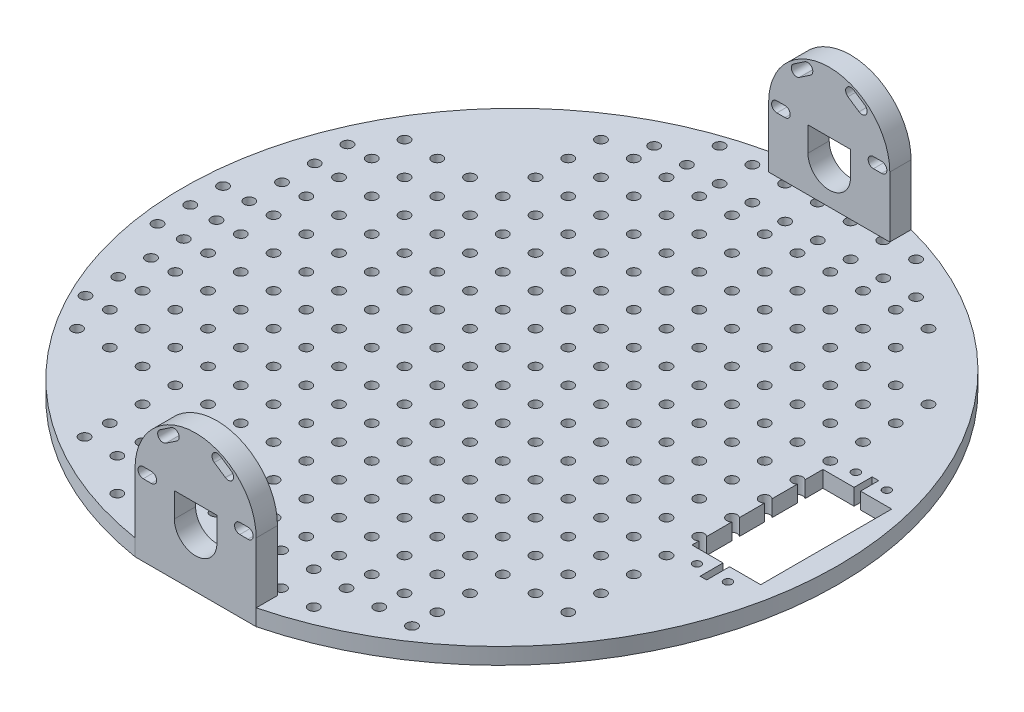
SolidWorks part; units mm, degrees
ref_plane "Ön Düzlem" through (0, 0, 0) normal (0, 0, 1) x (1, 0, 0)
ref_plane "Üst Düzlem" through (0, 0, 0) normal (0, 1, 0) x (1, 0, 0)
ref_plane "Sağ Düzlem" through (0, 0, 0) normal (1, 0, 0) x (0, 0, -1)
sketch "Çizim1" plane through (0, 0, 0) normal (0, 0, 1) x (1, 0, 0)
  circle A0 centre (0, 0) radius 18.5
  dimension "D1" = 37
extrude "Yükseklik-Ekstrüzyon1" add sketch "Çizim1" along normal blind 6.5
sketch "Çizim2" plane through (0, 0, 6.5) normal (0, 0, 1) x (1, 0, 0)
  line L0 (0, 0) -> (0, -7.5) construction
  line L1 (6.5, 0) -> (6.5, -7.5)
  line L2 (-6.5, 0) -> (-6.5, -7.5)
  line L3 (-6.5, 0) -> (6.5, 0)
  line L4 (-16, 0) -> (-13.5, 0) construction
  line L5 (-16, 1.6) -> (-13.5, 1.6)
  line L6 (-16, -1.6) -> (-13.5, -1.6)
  line L7 (16, 0) -> (13.5, 0) construction
  line L8 (16, -1.6) -> (13.5, -1.6)
  line L9 (16, 1.6) -> (13.5, 1.6)
  line L10 (6.6131, 14.8617) -> (9.9935, 12.5729) construction
  line L11 (7.5102, 16.1866) -> (10.8905, 13.8978)
  line L12 (5.7161, 13.5368) -> (9.0964, 11.2481)
  line L13 (-6.6131, 14.8617) -> (-9.9935, 12.5729) construction
  line L14 (-7.5102, 16.1866) -> (-10.8905, 13.8978)
  line L15 (-5.7161, 13.5368) -> (-9.0964, 11.2481)
  arc A0 (-16, 1.6) -> (-16, -1.6) centre (-16, 0) ccw
  arc A1 (-6.5, -7.5) -> (6.5, -7.5) centre (0, -7.5) ccw
  circle A2 centre (0, 0) radius 18.5 construction
  arc A3 (-13.5, -1.6) -> (-13.5, 1.6) centre (-13.5, 0) ccw
  arc A4 (16, -1.6) -> (16, 1.6) centre (16, 0) ccw
  arc A5 (13.5, 1.6) -> (13.5, -1.6) centre (13.5, 0) ccw
  arc A6 (7.5102, 16.1866) -> (5.7161, 13.5368) centre (6.6131, 14.8617) ccw
  arc A7 (9.0964, 11.2481) -> (10.8905, 13.8978) centre (9.9935, 12.5729) ccw
  arc A8 (-7.5102, 16.1866) -> (-5.7161, 13.5368) centre (-6.6131, 14.8617) cw
  arc A9 (-9.0964, 11.2481) -> (-10.8905, 13.8978) centre (-9.9935, 12.5729) cw
  point P3 (0, 0)
  point P6 (-14.75, 0)
  point P17 (14.75, 0)
  point P24 (8.3033, 13.7173)
  point P43 (-8.3033, 13.7173)
  dimension "D1" = 6.5
  dimension "D2" = 7.5
  dimension "D3" = 1.6
  dimension "D4" = 1.6
  dimension "D9" = 1.6
  dimension "D5" = 2.5
  dimension "D6" = 2.5
  dimension "D7" = 13.5
  dimension "D8" = 13.5
extrude "Kes-Ekstrüzyon1" cut sketch "Çizim2" against normal blind 6.5
sketch "Çizim3" plane through (0, 0, 0) normal (0, 0, -1) x (-1, 0, 0)
  line L0 (18.5, 0) -> (18.5, -18.5)
  line L1 (18.5, -18.5) -> (-18.5, -18.5)
  line L2 (-18.5, -18.5) -> (-18.5, 0)
  circle A0 centre (0, 0) radius 18.5 construction
  circle A2 centre (0, 0) radius 18.5
  circle A3 centre (0, 0) radius 18.5
  circle M22 centre (0, 0) radius 18.5
  dimension "D1" = 0
extrude "Yükseklik-Ekstrüzyon2" add sketch "Çizim3" against normal blind 6.5 contours L2 L1 M22 | L1 L0 M22 region at (-14.3677, -14.3677, 0) region at (14.3677, -14.3677, 0)
sketch "Çizim4" plane through (0, 0, 6.5) normal (0, 0, 1) x (1, 0, 0)
  line L1 (-18.5, -18.5) -> (18.5, -18.5)
  line L2 (-18.5, -18.5) -> (-18.5, -22.5)
  line L3 (-18.5, -22.5) -> (18.5, -22.5)
  line L4 (18.5, -18.5) -> (18.5, -22.5)
  dimension "D1" = 4
extrude "Yükseklik-Ekstrüzyon3" add sketch "Çizim4" along normal blind 30 and the other way up to surface (6.5 mm away) other way up to face at (-14.75, 0, 0)
sketch "Çizim5" plane through (0, -22.5, 0) normal (0, -1, 0) x (1, 0, 0)
  line L1 (-18.5, 0) -> (18.4954, 0)
  line L2 (-18.5, 0) -> (-18.5, 200)
  line L3 (-18.5, 200) -> (18.4954, 200)
  line L4 (18.4954, 0) -> (18.4954, 200)
  dimension "D1" = 200
extrude "Yükseklik-Ekstrüzyon4" add sketch "Çizim5" against normal up to surface (4 mm away) up to face at (0, -18.5, 21.5)
sketch "Çizim10" plane through (0, 0, 200) normal (0, 0, 1) x (1, 0, 0)
  line L0 (5.7161, 13.5368) -> (9.0964, 11.2481) construction
  line L1 (10.8905, 13.8978) -> (7.5102, 16.1866) construction
  line L2 (-7.5102, 16.1866) -> (-10.8905, 13.8978) construction
  line L3 (-18.5, 0) -> (-18.5, -18.5)
  line L4 (-18.5, -18.5) -> (18.5, -18.5)
  line L5 (18.5, -18.5) -> (18.5, 0)
  line L6 (-18.5, 0) -> (-18.5, -18.5)
  line L7 (-18.5, -18.5) -> (18.5, -18.5)
  line L8 (18.5, -18.5) -> (18.5, 0)
  line L9 (-9.0964, 11.2481) -> (-5.7161, 13.5368) construction
  line L10 (-13.5, 1.6) -> (-16, 1.6) construction
  line L11 (-16, -1.6) -> (-13.5, -1.6) construction
  line L12 (6.5, -7.5) -> (6.5, 0) construction
  line L13 (13.5, -1.6) -> (16, -1.6) construction
  line L14 (16, 1.6) -> (13.5, 1.6) construction
  line L15 (6.5, 0) -> (-6.5, 0) construction
  line L16 (-6.5, 0) -> (-6.5, -7.5) construction
  line L17 (5.7161, 13.5368) -> (9.0964, 11.2481)
  line L18 (10.8905, 13.8978) -> (7.5102, 16.1866)
  line L19 (-7.5102, 16.1866) -> (-10.8905, 13.8978)
  line L20 (-9.0964, 11.2481) -> (-5.7161, 13.5368)
  line L21 (-13.5, 1.6) -> (-16, 1.6)
  line L22 (-16, -1.6) -> (-13.5, -1.6)
  line L23 (6.5, -7.5) -> (6.5, 0)
  line L24 (13.5, -1.6) -> (16, -1.6)
  line L25 (16, 1.6) -> (13.5, 1.6)
  line L26 (6.5, 0) -> (-6.5, 0)
  line L27 (-6.5, 0) -> (-6.5, -7.5)
  arc A0 (9.0964, 11.2481) -> (10.8905, 13.8978) centre (9.9935, 12.5729) ccw construction
  arc A1 (18.5, 0) -> (-18.5, 0) centre (0, 0) ccw
  arc A2 (18.5, 0) -> (-18.5, 0) centre (0, 0) ccw
  arc A3 (7.5102, 16.1866) -> (5.7161, 13.5368) centre (6.6131, 14.8617) ccw construction
  arc A4 (-5.7161, 13.5368) -> (-7.5102, 16.1866) centre (-6.6131, 14.8617) ccw construction
  arc A5 (-10.8905, 13.8978) -> (-9.0964, 11.2481) centre (-9.9935, 12.5729) ccw construction
  arc A6 (-13.5, -1.6) -> (-13.5, 1.6) centre (-13.5, 0) ccw construction
  arc A7 (-16, 1.6) -> (-16, -1.6) centre (-16, 0) ccw construction
  arc A8 (-6.5, -7.5) -> (6.5, -7.5) centre (0, -7.5) ccw construction
  arc A9 (16, -1.6) -> (16, 1.6) centre (16, 0) ccw construction
  arc A10 (13.5, 1.6) -> (13.5, -1.6) centre (13.5, 0) ccw construction
  arc A11 (9.0964, 11.2481) -> (10.8905, 13.8978) centre (9.9935, 12.5729) ccw
  arc A12 (7.5102, 16.1866) -> (5.7161, 13.5368) centre (6.6131, 14.8617) ccw
  arc A13 (-5.7161, 13.5368) -> (-7.5102, 16.1866) centre (-6.6131, 14.8617) ccw
  arc A14 (-10.8905, 13.8978) -> (-9.0964, 11.2481) centre (-9.9935, 12.5729) ccw
  arc A15 (-13.5, -1.6) -> (-13.5, 1.6) centre (-13.5, 0) ccw
  arc A16 (-16, 1.6) -> (-16, -1.6) centre (-16, 0) ccw
  arc A17 (-6.5, -7.5) -> (6.5, -7.5) centre (0, -7.5) ccw
  arc A18 (16, -1.6) -> (16, 1.6) centre (16, 0) ccw
  arc A19 (13.5, 1.6) -> (13.5, -1.6) centre (13.5, 0) ccw
  dimension "D1" = 0
extrude "Yükseklik-Ekstrüzyon6" add sketch "Çizim10" against normal blind 6.5
sketch "Çizim12" plane through (0, -18.5, 0) normal (0, 1, 0) x (1, 0, 0)
  line L0 (-18.5, 0) -> (-18.5, -200)
  arc A0 (-18.5, 0) -> (-18.5, -200) centre (-2.5422, -100) ccw
extrude "Yükseklik-Ekstrüzyon7" add sketch "Çizim12" against normal up to surface (4 mm away) up to face at (6.1651, -22.5, 78.8333)
sketch "Çizim14" plane through (0, -22.5, 0) normal (0, -1, 0) x (1, 0, 0)
  line L5 (18.5, 36.5) -> (18.4954, 36.5)
  line L6 (18.4954, 36.5) -> (18.4954, 200)
  line L7 (18.4954, 200) -> (-18.5, 200)
  line L8 (-18.5, 0) -> (18.5, 0)
  line L9 (18.5, 0) -> (18.5, 36.5)
  line L10 (18.5, 36.5) -> (18.4954, 36.5)
  line L11 (18.4954, 36.5) -> (18.4954, 200)
  line L12 (18.4954, 200) -> (-18.5, 200)
  line L13 (-18.5, 0) -> (18.5, 0)
  line L14 (18.5, 0) -> (18.5, 36.5)
  arc A1 (-18.5, 200) -> (-18.5, 0) centre (-2.5422, 100) ccw
  arc A2 (-18.5, 200) -> (-18.5, 0) centre (-2.5422, 100) ccw
  dimension "D1" = 0
extrude "Yükseklik-Ekstrüzyon8" add sketch "Çizim14" along normal blind 6
sketch "Çizim16" plane through (0, -18.5, 0) normal (0, 1, 0) x (1, 0, 0)
  line L0 (-18.5, 0) -> (18.5, 0)
  line L1 (18.5, -200) -> (-18.5, -200)
  line L7 (18.5, -6.5) -> (-18.5, -6.5)
  line L8 (-18.5, -6.5) -> (-18.5, 0)
  line L9 (-18.5, -200) -> (-18.5, -193.5)
  line L10 (-18.5, -193.5) -> (18.4954, -193.5)
  line L11 (18.4954, -193.5) -> (18.4954, -36.5)
  line L12 (18.4954, -36.5) -> (18.5, -36.5)
  line L13 (18.5, -36.5) -> (18.5, -6.5)
  line L14 (18.5, -6.5) -> (-18.5, -6.5)
  line L15 (-18.5, -6.5) -> (-18.5, 0)
  line L16 (-18.5, -200) -> (-18.5, -193.5)
  line L17 (-18.5, -193.5) -> (18.4954, -193.5)
  line L18 (18.4954, -193.5) -> (18.4954, -36.5)
  line L19 (18.4954, -36.5) -> (18.5, -36.5)
  line L20 (18.5, -36.5) -> (18.5, -6.5)
  arc A0 (18.5, 0) -> (18.5, -200) centre (-7.01, -100) cw
  arc A1 (-18.5, 0) -> (-18.5, -200) centre (-2.5422, -100) ccw construction
  arc A3 (-18.5, 0) -> (-18.5, -200) centre (-2.5422, -100) ccw
  arc A4 (-18.5, 0) -> (-18.5, -200) centre (-2.5422, -100) ccw
  point P8 (-103.8075, -100)
  point P9 (96.1925, -100)
  dimension "D1" = 200
  dimension "D2" = 0
extrude "Yükseklik-Ekstrüzyon11" add sketch "Çizim16" against normal blind 10 contours A0 L0 L15 L14 L20 L19 L18 L17 L16 L1 | L20 L14 L15 A4 L16 L17 L18 L19 region at (48.8252, -18.5, 100.0009) region at (-35.3118, -18.5, 99.9995)
sketch "Çizim17" plane through (0, -18.5, 0) normal (0, 1, 0) x (1, 0, 0)
  line L2 (47.3144, -153.5135) -> (47.3144, -143.5135) construction
  circle A0 centre (-52.6856, -23.5135) radius 1.6
  circle A1 centre (-42.6856, -23.5135) radius 1.6
  circle A2 centre (-32.6856, -23.5135) radius 1.6
  circle A3 centre (-22.6856, -23.5135) radius 1.6
  circle A4 centre (-12.6856, -23.5135) radius 1.6
  circle A5 centre (-2.6856, -23.5135) radius 1.6
  circle A6 centre (7.3144, -23.5135) radius 1.6
  circle A7 centre (17.3144, -23.5135) radius 1.6
  circle A8 centre (27.3144, -23.5135) radius 1.6
  circle A9 centre (37.3144, -23.5135) radius 1.6
  circle A10 centre (47.3144, -23.5135) radius 1.6
  circle A11 centre (-42.6856, -33.5135) radius 1.6
  circle A12 centre (-32.6856, -33.5135) radius 1.6
  circle A13 centre (-22.6856, -33.5135) radius 1.6
  circle A14 centre (-12.6856, -33.5135) radius 1.6
  circle A15 centre (-2.6856, -33.5135) radius 1.6
  circle A16 centre (7.3144, -33.5135) radius 1.6
  circle A17 centre (17.3144, -33.5135) radius 1.6
  circle A18 centre (27.3144, -33.5135) radius 1.6
  circle A19 centre (37.3144, -33.5135) radius 1.6
  circle A20 centre (47.3144, -33.5135) radius 1.6
  circle A21 centre (-42.6856, -43.5135) radius 1.6
  circle A22 centre (-32.6856, -43.5135) radius 1.6
  circle A23 centre (-22.6856, -43.5135) radius 1.6
  circle A24 centre (-12.6856, -43.5135) radius 1.6
  circle A25 centre (-2.6856, -43.5135) radius 1.6
  circle A26 centre (7.3144, -43.5135) radius 1.6
  circle A27 centre (17.3144, -43.5135) radius 1.6
  circle A28 centre (27.3144, -43.5135) radius 1.6
  circle A29 centre (37.3144, -43.5135) radius 1.6
  circle A30 centre (47.3144, -43.5135) radius 1.6
  circle A31 centre (-42.6856, -53.5135) radius 1.6
  circle A32 centre (-32.6856, -53.5135) radius 1.6
  circle A33 centre (-22.6856, -53.5135) radius 1.6
  circle A34 centre (-12.6856, -53.5135) radius 1.6
  circle A35 centre (-2.6856, -53.5135) radius 1.6
  circle A36 centre (7.3144, -53.5135) radius 1.6
  circle A37 centre (17.3144, -53.5135) radius 1.6
  circle A38 centre (27.3144, -53.5135) radius 1.6
  circle A39 centre (37.3144, -53.5135) radius 1.6
  circle A40 centre (47.3144, -53.5135) radius 1.6
  circle A41 centre (-42.6856, -63.5135) radius 1.6
  circle A42 centre (-32.6856, -63.5135) radius 1.6
  circle A43 centre (-22.6856, -63.5135) radius 1.6
  circle A44 centre (-12.6856, -63.5135) radius 1.6
  circle A45 centre (-2.6856, -63.5135) radius 1.6
  circle A46 centre (7.3144, -63.5135) radius 1.6
  circle A47 centre (17.3144, -63.5135) radius 1.6
  circle A48 centre (27.3144, -63.5135) radius 1.6
  circle A49 centre (37.3144, -63.5135) radius 1.6
  circle A50 centre (47.3144, -63.5135) radius 1.6
  circle A51 centre (-42.6856, -73.5135) radius 1.6
  circle A52 centre (-32.6856, -73.5135) radius 1.6
  circle A53 centre (-22.6856, -73.5135) radius 1.6
  circle A54 centre (-12.6856, -73.5135) radius 1.6
  circle A55 centre (-2.6856, -73.5135) radius 1.6
  circle A56 centre (7.3144, -73.5135) radius 1.6
  circle A57 centre (17.3144, -73.5135) radius 1.6
  circle A58 centre (27.3144, -73.5135) radius 1.6
  circle A59 centre (37.3144, -73.5135) radius 1.6
  circle A60 centre (47.3144, -73.5135) radius 1.6
  circle A61 centre (-42.6856, -83.5135) radius 1.6
  circle A62 centre (-32.6856, -83.5135) radius 1.6
  circle A63 centre (-22.6856, -83.5135) radius 1.6
  circle A64 centre (-12.6856, -83.5135) radius 1.6
  circle A65 centre (-2.6856, -83.5135) radius 1.6
  circle A66 centre (7.3144, -83.5135) radius 1.6
  circle A67 centre (17.3144, -83.5135) radius 1.6
  circle A68 centre (27.3144, -83.5135) radius 1.6
  circle A69 centre (37.3144, -83.5135) radius 1.6
  circle A70 centre (47.3144, -83.5135) radius 1.6
  circle A71 centre (-42.6856, -93.5135) radius 1.6
  circle A72 centre (-32.6856, -93.5135) radius 1.6
  circle A73 centre (-22.6856, -93.5135) radius 1.6
  circle A74 centre (-12.6856, -93.5135) radius 1.6
  circle A75 centre (-2.6856, -93.5135) radius 1.6
  circle A76 centre (7.3144, -93.5135) radius 1.6
  circle A77 centre (17.3144, -93.5135) radius 1.6
  circle A78 centre (27.3144, -93.5135) radius 1.6
  circle A79 centre (37.3144, -93.5135) radius 1.6
  circle A80 centre (47.3144, -93.5135) radius 1.6
  circle A81 centre (-42.6856, -103.5135) radius 1.6
  circle A82 centre (-32.6856, -103.5135) radius 1.6
  circle A83 centre (-22.6856, -103.5135) radius 1.6
  circle A84 centre (-12.6856, -103.5135) radius 1.6
  circle A85 centre (-2.6856, -103.5135) radius 1.6
  circle A86 centre (7.3144, -103.5135) radius 1.6
  circle A87 centre (17.3144, -103.5135) radius 1.6
  circle A88 centre (27.3144, -103.5135) radius 1.6
  circle A89 centre (37.3144, -103.5135) radius 1.6
  circle A90 centre (47.3144, -103.5135) radius 1.6
  circle A91 centre (-42.6856, -113.5135) radius 1.6
  circle A92 centre (-32.6856, -113.5135) radius 1.6
  circle A93 centre (-22.6856, -113.5135) radius 1.6
  circle A94 centre (-12.6856, -113.5135) radius 1.6
  circle A95 centre (-2.6856, -113.5135) radius 1.6
  circle A96 centre (7.3144, -113.5135) radius 1.6
  circle A97 centre (17.3144, -113.5135) radius 1.6
  circle A98 centre (27.3144, -113.5135) radius 1.6
  circle A99 centre (37.3144, -113.5135) radius 1.6
  circle A100 centre (47.3144, -113.5135) radius 1.6
  circle A101 centre (-42.6856, -123.5135) radius 1.6
  circle A102 centre (-32.6856, -123.5135) radius 1.6
  circle A103 centre (-22.6856, -123.5135) radius 1.6
  circle A104 centre (-12.6856, -123.5135) radius 1.6
  circle A105 centre (-2.6856, -123.5135) radius 1.6
  circle A106 centre (7.3144, -123.5135) radius 1.6
  circle A107 centre (17.3144, -123.5135) radius 1.6
  circle A108 centre (27.3144, -123.5135) radius 1.6
  circle A109 centre (37.3144, -123.5135) radius 1.6
  circle A110 centre (47.3144, -123.5135) radius 1.6
  circle A111 centre (-42.6856, -133.5135) radius 1.6
  circle A112 centre (-32.6856, -133.5135) radius 1.6
  circle A113 centre (-22.6856, -133.5135) radius 1.6
  circle A114 centre (-12.6856, -133.5135) radius 1.6
  circle A115 centre (-2.6856, -133.5135) radius 1.6
  circle A116 centre (7.3144, -133.5135) radius 1.6
  circle A117 centre (17.3144, -133.5135) radius 1.6
  circle A118 centre (27.3144, -133.5135) radius 1.6
  circle A119 centre (37.3144, -133.5135) radius 1.6
  circle A120 centre (47.3144, -133.5135) radius 1.6
  circle A121 centre (-42.6856, -143.5135) radius 1.6
  circle A122 centre (-32.6856, -143.5135) radius 1.6
  circle A123 centre (-22.6856, -143.5135) radius 1.6
  circle A124 centre (-12.6856, -143.5135) radius 1.6
  circle A125 centre (-2.6856, -143.5135) radius 1.6
  circle A126 centre (7.3144, -143.5135) radius 1.6
  circle A127 centre (17.3144, -143.5135) radius 1.6
  circle A128 centre (27.3144, -143.5135) radius 1.6
  circle A129 centre (37.3144, -143.5135) radius 1.6
  circle A130 centre (47.3144, -143.5135) radius 1.6
  circle A131 centre (-42.6856, -153.5135) radius 1.6
  circle A132 centre (-32.6856, -153.5135) radius 1.6
  circle A133 centre (-22.6856, -153.5135) radius 1.6
  circle A134 centre (-12.6856, -153.5135) radius 1.6
  circle A135 centre (-2.6856, -153.5135) radius 1.6
  circle A136 centre (7.3144, -153.5135) radius 1.6
  circle A137 centre (17.3144, -153.5135) radius 1.6
  circle A138 centre (27.3144, -153.5135) radius 1.6
  circle A139 centre (37.3144, -153.5135) radius 1.6
  circle A140 centre (47.3144, -153.5135) radius 1.6
  circle A141 centre (-42.6856, -163.5135) radius 1.6
  circle A142 centre (-32.6856, -163.5135) radius 1.6
  circle A143 centre (-22.6856, -163.5135) radius 1.6
  circle A144 centre (-12.6856, -163.5135) radius 1.6
  circle A145 centre (-2.6856, -163.5135) radius 1.6
  circle A146 centre (7.3144, -163.5135) radius 1.6
  circle A147 centre (17.3144, -163.5135) radius 1.6
  circle A148 centre (27.3144, -163.5135) radius 1.6
  circle A149 centre (37.3144, -163.5135) radius 1.6
  circle A150 centre (47.3144, -163.5135) radius 1.6
  circle A151 centre (-42.6856, -173.5135) radius 1.6
  circle A152 centre (-32.6856, -173.5135) radius 1.6
  circle A153 centre (-22.6856, -173.5135) radius 1.6
  circle A154 centre (-12.6856, -173.5135) radius 1.6
  circle A155 centre (-2.6856, -173.5135) radius 1.6
  circle A156 centre (7.3144, -173.5135) radius 1.6
  circle A157 centre (17.3144, -173.5135) radius 1.6
  circle A158 centre (27.3144, -173.5135) radius 1.6
  circle A159 centre (37.3144, -173.5135) radius 1.6
  circle A160 centre (47.3144, -173.5135) radius 1.6
  circle A161 centre (-52.6856, -33.5135) radius 1.6
  circle A162 centre (-52.6856, -43.5135) radius 1.6
  circle A163 centre (-52.6856, -53.5135) radius 1.6
  circle A164 centre (-52.6856, -63.5135) radius 1.6
  circle A165 centre (-52.6856, -73.5135) radius 1.6
  circle A166 centre (-52.6856, -83.5135) radius 1.6
  circle A167 centre (-52.6856, -93.5135) radius 1.6
  circle A168 centre (-52.6856, -103.5135) radius 1.6
  circle A169 centre (-52.6856, -113.5135) radius 1.6
  circle A170 centre (-52.6856, -123.5135) radius 1.6
  circle A171 centre (-52.6856, -133.5135) radius 1.6
  circle A172 centre (-52.6856, -143.5135) radius 1.6
  circle A173 centre (-52.6856, -153.5135) radius 1.6
  circle A174 centre (-52.6856, -163.5135) radius 1.6
  circle A175 centre (-52.6856, -173.5135) radius 1.6
  circle A176 centre (-62.6856, -93.5135) radius 1.6
  circle A177 centre (-72.6856, -93.5135) radius 1.6
  circle A178 centre (-82.6856, -93.5135) radius 1.6
  circle A179 centre (-62.6856, -83.5135) radius 1.6
  circle A180 centre (-72.6856, -83.5135) radius 1.6
  circle A181 centre (-82.6856, -83.5135) radius 1.6
  circle A182 centre (-62.6856, -73.5135) radius 1.6
  circle A183 centre (-72.6856, -73.5135) radius 1.6
  circle A184 centre (-82.6856, -73.5135) radius 1.6
  circle A185 centre (-62.6856, -63.5135) radius 1.6
  circle A186 centre (-72.6856, -63.5135) radius 1.6
  circle A187 centre (-82.6856, -63.5135) radius 1.6
  circle A188 centre (-62.6856, -53.5135) radius 1.6
  circle A189 centre (-72.6856, -53.5135) radius 1.6
  circle A190 centre (-82.6856, -53.5135) radius 1.6
  circle A191 centre (-52.6856, -83.5135) radius 1.6
  circle A192 centre (-52.6856, -73.5135) radius 1.6
  circle A193 centre (-52.6856, -63.5135) radius 1.6
  circle A194 centre (-52.6856, -53.5135) radius 1.6
  circle A195 centre (-62.6856, -103.5135) radius 1.6
  circle A196 centre (-72.6856, -103.5135) radius 1.6
  circle A197 centre (-82.6856, -103.5135) radius 1.6
  circle A198 centre (-62.6856, -113.5135) radius 1.6
  circle A199 centre (-72.6856, -113.5135) radius 1.6
  circle A200 centre (-82.6856, -113.5135) radius 1.6
  circle A201 centre (-62.6856, -123.5135) radius 1.6
  circle A202 centre (-72.6856, -123.5135) radius 1.6
  circle A203 centre (-82.6856, -123.5135) radius 1.6
  circle A204 centre (-62.6856, -133.5135) radius 1.6
  circle A205 centre (-72.6856, -133.5135) radius 1.6
  circle A206 centre (-82.6856, -133.5135) radius 1.6
  circle A207 centre (-62.6856, -143.5135) radius 1.6
  circle A208 centre (-72.6856, -143.5135) radius 1.6
  circle A209 centre (-82.6856, -143.5135) radius 1.6
  circle A210 centre (-62.6856, -153.5135) radius 1.6
  circle A211 centre (-72.6856, -153.5135) radius 1.6
  circle A212 centre (-82.6856, -153.5135) radius 1.6
  circle A213 centre (-52.6856, -113.5135) radius 1.6
  circle A214 centre (-52.6856, -123.5135) radius 1.6
  circle A215 centre (-52.6856, -133.5135) radius 1.6
  circle A216 centre (-52.6856, -143.5135) radius 1.6
  circle A217 centre (-52.6856, -153.5135) radius 1.6
  circle A218 centre (57.3144, -153.5135) radius 1.6
  circle A219 centre (67.3144, -153.5135) radius 1.6
  circle A220 centre (57.3144, -143.5135) radius 1.6
  circle A221 centre (67.3144, -143.5135) radius 1.6
  circle A222 centre (57.3144, -133.5135) radius 1.6
  circle A223 centre (67.3144, -133.5135) radius 1.6
  circle A224 centre (57.3144, -123.5135) radius 1.6
  circle A225 centre (67.3144, -123.5135) radius 1.6
  circle A226 centre (57.3144, -113.5135) radius 1.6
  circle A227 centre (67.3144, -113.5135) radius 1.6
  circle A228 centre (57.3144, -103.5135) radius 1.6
  circle A229 centre (67.3144, -103.5135) radius 1.6
  circle A230 centre (57.3144, -93.5135) radius 1.6
  circle A231 centre (67.3144, -93.5135) radius 1.6
  circle A232 centre (57.3144, -83.5135) radius 1.6
  circle A233 centre (67.3144, -83.5135) radius 1.6
  circle A234 centre (57.3144, -73.5135) radius 1.6
  circle A235 centre (67.3144, -73.5135) radius 1.6
  circle A236 centre (57.3144, -63.5135) radius 1.6
  circle A237 centre (67.3144, -63.5135) radius 1.6
  circle A238 centre (57.3144, -53.5135) radius 1.6
  circle A239 centre (67.3144, -53.5135) radius 1.6
  circle A240 centre (57.3144, -43.5135) radius 1.6
  circle A241 centre (67.3144, -43.5135) radius 1.6
  circle A242 centre (47.3144, -143.5135) radius 1.6
  circle A243 centre (47.3144, -133.5135) radius 1.6
  circle A244 centre (47.3144, -123.5135) radius 1.6
  circle A245 centre (47.3144, -113.5135) radius 1.6
  circle A246 centre (47.3144, -103.5135) radius 1.6
  circle A247 centre (47.3144, -93.5135) radius 1.6
  circle A248 centre (47.3144, -83.5135) radius 1.6
  circle A249 centre (47.3144, -73.5135) radius 1.6
  circle A250 centre (47.3144, -63.5135) radius 1.6
  circle A251 centre (47.3144, -53.5135) radius 1.6
  circle A252 centre (47.3144, -43.5135) radius 1.6
  dimension "D1" = 3.2
  dimension "D10" = 10
  dimension "D2" = 11
  dimension "D3" = 16
  dimension "D4" = 4
  dimension "D5" = 5
  dimension "D6" = 4
  dimension "D7" = 6
  dimension "D8" = 3
  dimension "D9" = 12
extrude "Kes-Ekstrüzyon2" cut sketch "Çizim17" against normal blind 95
sketch "Çizim18" plane through (0, -18.5, 0) normal (0, 1, 0) x (1, 0, 0)
  line L0 (89.4166, -76.8405) -> (89.4166, -116.8405)
  line L1 (89.4166, -116.8405) -> (79.9176, -116.8405)
  line L2 (68.4186, -116.8405) -> (68.4186, -76.8405)
  line L3 (68.4186, -76.8405) -> (77.9176, -76.8405)
  line L4 (79.9176, -76.8405) -> (79.9176, -71.3062)
  line L5 (77.9176, -76.8405) -> (77.9176, -71.3062)
  line L22 (77.9176, -71.3062) -> (79.9176, -71.3062)
  line L23 (79.9176, -123.8405) -> (77.9176, -123.8405)
  line L24 (79.9176, -123.8405) -> (79.9176, -116.8405)
  line L25 (77.9176, -123.8405) -> (77.9176, -116.8405)
  line L26 (79.9176, -76.8405) -> (89.4166, -76.8405)
  line L27 (77.9176, -116.8405) -> (68.4186, -116.8405)
  circle A0 centre (83.6643, -121.0872) radius 1.2435
  circle A1 centre (74.1725, -121.0568) radius 1.206
  circle A2 centre (83.6639, -72.5758) radius 1.224
  circle A3 centre (74.1976, -72.5669) radius 1.2367
extrude "Kes-Ekstrüzyon3" cut sketch "Çizim18" against normal blind 95
sketch "Çizim20" plane through (0, -28.5, 0) normal (0, -1, 0) x (1, 0, 0)
  circle A1 centre (-52.9117, 181.0035) radius 1.6
  circle A2 centre (-42.9117, 181.0035) radius 1.6
  circle A3 centre (-32.9117, 181.0035) radius 1.6
  circle A4 centre (-22.9117, 181.0035) radius 1.6
  circle A5 centre (-12.9117, 181.0035) radius 1.6
  circle A6 centre (-2.9117, 181.0035) radius 1.6
  circle A7 centre (7.0883, 181.0035) radius 1.6
  circle A8 centre (17.0883, 181.0035) radius 1.6
  circle A9 centre (27.0883, 181.0035) radius 1.6
  circle A10 centre (37.0883, 181.0035) radius 1.6
  circle A11 centre (47.0883, 181.0035) radius 1.6
  circle A12 centre (-42.9117, 17.059) radius 1.6
  circle A13 centre (-32.9117, 191.0035) radius 1.6
  circle A14 centre (-22.9117, 191.0035) radius 1.6
  circle A15 centre (-12.9117, 191.0035) radius 1.6
  circle A16 centre (-2.9117, 191.0035) radius 1.6
  circle A17 centre (7.0883, 191.0035) radius 1.6
  circle A18 centre (17.0883, 191.0035) radius 1.6
  circle A19 centre (27.0883, 191.0035) radius 1.6
  circle A20 centre (-32.9117, 17.059) radius 1.6
  circle A21 centre (-22.9117, 17.059) radius 1.6
  circle A22 centre (-12.9117, 17.059) radius 1.6
  circle A23 centre (-52.9117, 191.0035) radius 1.6 [skipped]
  circle A24 centre (47.0883, 191.0035) radius 1.6 [skipped]
  circle A25 centre (37.0883, 191.0035) radius 1.6 [skipped]
  circle A26 centre (-42.9117, 191.0035) radius 1.6 [skipped]
  circle A27 centre (-2.9117, 17.059) radius 1.6
  circle A28 centre (7.0883, 17.059) radius 1.6
  circle A29 centre (17.0883, 17.059) radius 1.6
  circle A30 centre (27.0883, 17.059) radius 1.6
  circle A31 centre (37.0883, 17.059) radius 1.6
  circle A32 centre (-32.9117, 7.059) radius 1.6
  circle A33 centre (-22.9117, 7.059) radius 1.6
  circle A34 centre (-12.9117, 7.059) radius 1.6
  circle A35 centre (-2.9117, 7.059) radius 1.6
  circle A36 centre (7.0883, 7.059) radius 1.6
  circle A37 centre (17.0883, 7.059) radius 1.6
  circle A38 centre (27.0883, 7.059) radius 1.6
  circle A39 centre (-90.1081, 143.5135) radius 1.6
  circle A41 centre (-42.9117, 7.059) radius 1.6 [skipped]
  circle A42 centre (37.0883, 7.059) radius 1.6 [skipped]
  circle A45 centre (-98.1081, 113.5135) radius 1.6
  circle A46 centre (-98.1081, 103.5135) radius 1.6
  circle A47 centre (-98.1081, 93.5135) radius 1.6
  circle A52 centre (-90.1081, 133.5135) radius 1.6
  circle A53 centre (-90.1081, 123.5135) radius 1.6
  circle A54 centre (-90.1081, 113.5135) radius 1.6
  circle A55 centre (-90.1081, 103.5135) radius 1.6
  circle A56 centre (-90.1081, 93.5135) radius 1.6
  circle A57 centre (-90.1081, 83.5135) radius 1.6
  circle A58 centre (-90.1081, 73.5135) radius 1.6
  circle A59 centre (-90.1081, 63.5135) radius 1.6
  circle A61 centre (-98.1081, 143.5135) radius 1.6 [skipped]
  circle A62 centre (-98.1081, 133.5135) radius 1.6 [skipped]
  circle A63 centre (-98.1081, 123.5135) radius 1.6 [skipped]
  circle A64 centre (-98.1081, 53.5135) radius 1.6 [skipped]
  circle A65 centre (-98.1081, 63.5135) radius 1.6 [skipped]
  circle A66 centre (-98.1081, 73.5135) radius 1.6 [skipped]
  circle A67 centre (-98.1081, 83.5135) radius 1.6 [skipped]
  circle A68 centre (-90.1081, 53.5135) radius 1.6 [skipped]
  dimension "D1" = 3.2
  dimension "D4" = 3.2
  dimension "D7" = 3.2
  dimension "D2" = 11
  dimension "D3" = 2
  dimension "D5" = 9
  dimension "D6" = 2
  dimension "D8" = 2
  dimension "D9" = 10
extrude "Kes-Ekstrüzyon4" cut sketch "Çizim20" against normal up to surface (10 mm away) up to face at (74.1976, -18.5, 73.8036)
sketch "Çizim21" plane through (0, -28.5, 0) normal (0, -1, 0) x (1, 0, 0)
  line L2 (-18.5, 0) -> (18.5, 0)
  line L3 (18.5, 200) -> (-18.5, 200)
  line L4 (-18.5, 0) -> (18.5, 0)
  line L5 (18.5, 200) -> (-18.5, 200)
  arc A2 (18.5, 0) -> (18.5, 200) centre (-7.01, 100) ccw
  arc A3 (-18.5, 200) -> (-18.5, 0) centre (-2.5422, 100) ccw
  arc A4 (18.5, 0) -> (18.5, 200) centre (-7.01, 100) ccw
  arc A5 (-18.5, 200) -> (-18.5, 0) centre (-2.5422, 100) ccw
  dimension "D1" = 0
extrude "Kes-Ekstrüzyon5" cut sketch "Çizim21" against normal blind 5
